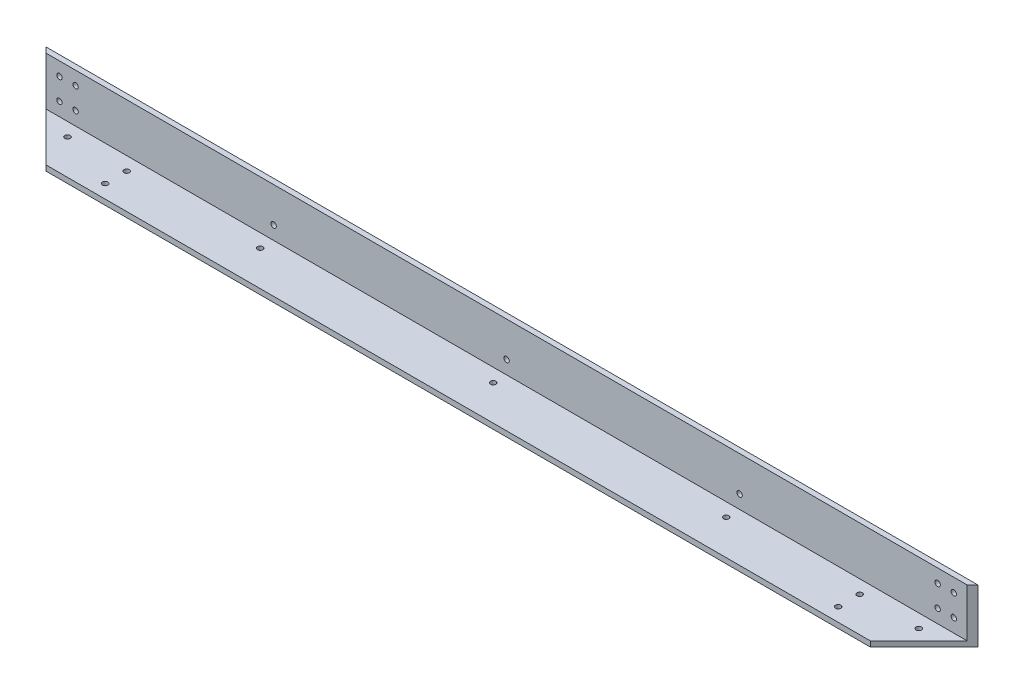
SolidWorks part; units mm, degrees
ref_plane "Front Plane" through (0, 0, 0) normal (0, 0, 1) x (1, 0, 0)
ref_plane "Top Plane" through (0, 0, 0) normal (0, 1, 0) x (1, 0, 0)
ref_plane "Right Plane" through (0, 0, 0) normal (1, 0, 0) x (0, 0, -1)
sketch "Sketch1" plane through (0, 0, 0) normal (1, 0, 0) x (0, 0, -1)
  line L0 (0, 0) -> (-31.75, 0)
  line L1 (-31.75, 0) -> (-31.75, 3.175)
  line L2 (-31.75, 3.175) -> (-3.175, 3.175)
  line L3 (-3.175, 3.175) -> (-3.175, 31.75)
  line L4 (-3.175, 31.75) -> (0, 31.75)
  line L5 (0, 31.75) -> (0, 0)
  dimension "LHeight" = 31.75
  dimension "LWidth" = 31.75
  dimension "LMaterialThickness" = 3.175
  dimension "D1" = 28.575
  dimension "D2" = 28.575
  dimension "D3" = 3.175
extrude "Boss-Extrude1" add sketch "Sketch1" along normal blind 550
chamfer "Chamfer6" distance 31.75 angle 45 1 edges at (550, 1.5875, 31.75)
chamfer "Chamfer7" distance 31.75 angle 45 1 edges at (0, 1.5875, 31.75)
sketch "TopHoles-Sketch3" plane through (0, 3.175, 0) normal (0, 1, 0) x (1, 0, 0)
  line L1 (518.25, -31.75) -> (31.75, -31.75) construction
  line L2 (550, 0) -> (0, 0) construction
  circle A5 centre (58.7375, -23.8125) radius 1.5875
  circle A6 centre (491.2625, -23.8125) radius 1.5875
  circle A9 centre (491.2625, -11.1125) radius 1.5875
  circle A10 centre (58.7375, -11.1125) radius 1.5875
  circle A11 centre (526.1875, -11.1125) radius 1.5875
  circle A12 centre (23.8125, -11.1125) radius 1.5875
  circle A13 centre (275, -11.1125) radius 1.5875
  circle A14 centre (137.5, -11.1125) radius 1.5875
  circle A15 centre (412.5, -11.1125) radius 1.5875
  dimension "D8" = 137.5
  dimension "D10" = 137.5
  dimension "D9" = 3.175
  dimension "D12" = 7.9375
  dimension "D2" = 11.1125
  dimension "D6" = 23.8125
  dimension "D3" = 23.8125
  dimension "D5" = 12.7
  dimension "D4" = 34.925
  dimension "D7" = 34.925
  dimension "D11" = 137.5
extrude "TopHoles-Cut-Extrude2" cut sketch "TopHoles-Sketch3" against normal through all
sketch "SideHoles-Sketch4" plane through (0, 0, 3.175) normal (0, 0, 1) x (1, 0, 0)
  line L0 (518.25, 0) -> (31.75, 0) construction
  line L3 (550, 31.75) -> (0, 31.75) construction
  line L4 (0, 0) -> (0, 31.75) construction
  line L5 (550, 0) -> (550, 31.75) construction
  circle A1 centre (11.1125, 23.8125) radius 1.5875
  circle A3 centre (529.3625, 23.8125) radius 1.5875
  circle A4 centre (20.6375, 23.8125) radius 1.5875
  circle A5 centre (538.8875, 23.8125) radius 1.5875
  circle A6 centre (11.1125, 11.1125) radius 1.5875
  circle A7 centre (20.6375, 11.1125) radius 1.5875
  circle A8 centre (529.3625, 11.1125) radius 1.5875
  circle A9 centre (538.8875, 11.1125) radius 1.5875
  circle A10 centre (137.5, 11.1125) radius 1.5875
  circle A11 centre (275, 11.1125) radius 1.5875
  circle A12 centre (412.5, 11.1125) radius 1.5875
  dimension "D2" = 3.175
  dimension "D4" = 7.9375
  dimension "D7" = 11.1125
  dimension "D1" = 11.1125
  dimension "D6" = 20.6375
  dimension "D3" = 11.1125
  dimension "D5" = 20.6375
  dimension "D8" = 137.5
  dimension "D9" = 137.5
  dimension "D10" = 137.5
extrude "SideHoles-Cut-Extrude3" cut sketch "SideHoles-Sketch4" against normal through all
equation "\"TopRailWidth\"= 1.25in"
equation "\"TopRailHeight\"= 1.25in"
equation "\"RailThickness\"= .125in'Spec"
equation "\"SideRailHoleY1FromEdge\"= \"HoleOffsetFromEdge\""
equation "\"SideRailHoleX1FromSide\"= \"HoleOffsetFromSide\""
equation "\"SideRailLength\"= 550mm"
equation "\"VSWidth\"= 1.25in'Spec"
equation "\"HoleOffsetFromEdge\"= \"RailThickness\" * 2.5"
equation "\"HoleOffsetFromSide\"= \"RailThickness\" * 3.5"
equation "\"TopCBWidth\"= \"TopRailWidth\" - \"RailThickness\"'Equals 28.575"
equation "\"SideRailHoleX2FromSide\"= \"VSWidth\" - \"HoleOffsetFromEdge\" - \"RailThickness\"'Equals 20.6375"
equation "\"FasteningHoleDiameter\"= .125in"
equation "\"SideRailHoleY2FromSide\"= \"HoleOffsetFromSide\""
equation "\"D2@SideHoles-Sketch4\"=\"FasteningHoleDiameter\""
equation "\"LWidth@Sketch1\"=\"TopRailWidth\""
equation "\"LHeight@Sketch1\"=\"TopRailHeight\""
equation "\"LMaterialThickness@Sketch1\"=\"RailThickness\""
equation "\"D1@Boss-Extrude1\"=\"SideRailLength\""
equation "\"D2@TopHoles-Sketch3\"=\"TopHoleY1FromSide\""
equation "\"D9@TopHoles-Sketch3\" = \"FasteningHoleDiameter\""
equation "\"D4@SideHoles-Sketch4\"=\"SideRailHoleY1FromEdge\""
equation "\"D1@Chamfer6\"=\"TopRailWidth\""
equation "\"D1@Chamfer7\"=\"TopRailWidth\""
equation "\"D7@SideHoles-Sketch4\"=\"SideRailHoleY2FromSide\""
equation "\"D1@SideHoles-Sketch4\"=\"SideRailHoleX1FromSide\""
equation "\"D6@SideHoles-Sketch4\"=\"SideRailHoleX2FromSide\""
equation "\"D3@SideHoles-Sketch4\"=\"SideRailHoleX1FromSide\""
equation "\"D5@SideHoles-Sketch4\"=\"SideRailHoleX2FromSide\""
equation "\"TopHoleY1FromSide\"= \"HoleOffsetFromSide\""
equation "\"TopHoleY2FromY1\"= \"TopCBWidth\" - \"TopHoleY1FromEdge\" - \"HoleOffsetFromEdge\"'Equals 12.7"
equation "\"TopHoleX1FromEdge\"= \"TopCBWidth\" - \"HoleOffsetFromEdge\"'Equals 20.6375"
equation "\"TopHoleX2FromX1\"= \"TopCBLength\" - \"TopHoleX1FromEdge\" - \"HoleOffsetFromEdge\"'Equals 34.925"
equation "\"D5@TopHoles-Sketch3\"=\"TopHoleY2FromY1\""
equation "\"D4@TopHoles-Sketch3\"=\"TopHoleX2FromX1\""
equation "\"D7@TopHoles-Sketch3\"=\"TopHoleX2FromX1\""
equation "\"D3@TopHoles-Sketch3\"=\"TopHoleX1FromEdge\" + \"RailThickness\""
equation "\"D6@TopHoles-Sketch3\"=\"TopHoleX1FromEdge\" + \"RailThickness\""
equation "\"TopCBLength\"= \"TopRailWidth\" * 2'Equals 63.5"
equation "\"TopHoleY1FromEdge\"= \"HoleOffsetFromEdge\""
equation "\"LeftOrRightEnclosureHoleOffsets\"= \"SideRailLength\" / 4"
equation "\"D8@TopHoles-Sketch3\"=\"LeftOrRightEnclosureHoleOffsets\""
equation "\"D10@TopHoles-Sketch3\"=\"LeftOrRightEnclosureHoleOffsets\""
equation "\"D11@TopHoles-Sketch3\"=\"LeftOrRightEnclosureHoleOffsets\""
equation "\"D8@SideHoles-Sketch4\"=\"LeftOrRightEnclosureHoleOffsets\""
equation "\"D9@SideHoles-Sketch4\"=\"LeftOrRightEnclosureHoleOffsets\""
equation "\"D10@SideHoles-Sketch4\"=\"LeftOrRightEnclosureHoleOffsets\""
